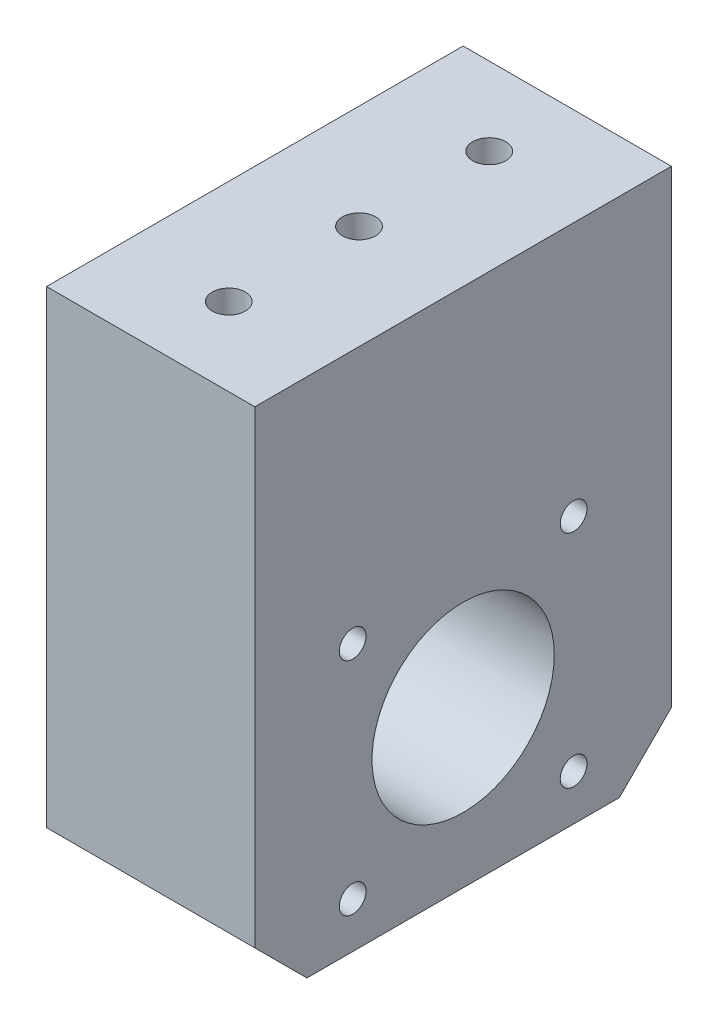
SolidWorks part; units mm, degrees
material "Nylon 6/10"
ref_plane "Front Plane" through (0, 0, 0) normal (0, 0, 1) x (1, 0, 0)
ref_plane "Top Plane" through (0, 0, 0) normal (0, 1, 0) x (1, 0, 0)
ref_plane "Right Plane" through (0, 0, 0) normal (1, 0, 0) x (0, 0, -1)
sketch "Sketch1" plane through (0, 0, 0) normal (1, 0, 0) x (0, 0, -1)
  line L1 (-25.4, -31.75) -> (25.4, -31.75)
  line L2 (-25.4, -31.75) -> (-25.4, 31.75)
  line L3 (-25.4, 31.75) -> (25.4, 31.75)
  line L4 (25.4, -31.75) -> (25.4, 31.75)
  line L5 (-25.4, -31.75) -> (25.4, 31.75) construction
  line L6 (-25.4, 31.75) -> (25.4, -31.75) construction
  point P0 (0, 0)
  dimension "D1" = 50.8
  dimension "D2" = 63.5
extrude "Base" add sketch "Sketch1" along normal blind 25.4
hole_wizard "7/8 (0.875) Diameter Hole1" positions "Sketch3" profile "Sketch2" hole size "7/8" standard "ANSI Inch" end condition through all
sketch "Sketch3" plane through (25.4, 0, 0) normal (1, 0, 0) x (0, 0, -1)
  line L1 (25.4, 31.75) -> (-25.4, 31.75) construction
  line L2 (0, -31.75) -> (0, 31.75) construction
  line L3 (-25.4, -31.75) -> (25.4, -31.75) construction
  point P0 (0, -12.7)
  dimension "D1" = 44.45
sketch "Sketch2" plane through (25.4, -12.7, 0) normal (0, 1, 0) x (0, 0, -1)
  line L0 (0, 0) -> (0, 25.4)
  line L1 (0, 25.4) -> (11.1125, 25.4)
  line L2 (11.1125, 25.4) -> (11.1125, 0)
  line L5 (11.1125, 0) -> (0, 0)
  line L11 (0, -6.35) -> (0, 107.95) construction
  dimension "Thru Hole Dia." = 22.225
  dimension "Thru Hole Depth" = 25.4
hole_wizard "#10-32 Tapped Hole1" positions "Sketch12" profile "Sketch11" tap size "#10-32" standard "ANSI Inch"
sketch "Sketch12" plane through (0, 31.75, 0) normal (0, 1, 0) x (1, 0, 0)
  line L0 (12.7, 25.4) -> (12.7, -25.4) construction
  line L1 (25.4, 25.4) -> (0, 25.4) construction
  line L2 (25.4, -25.4) -> (0, -25.4) construction
  line L3 (25.4, 0) -> (0, 0) construction
  line L4 (25.4, 25.4) -> (25.4, -25.4) construction
  line L5 (0, 25.4) -> (0, -25.4) construction
  point P0 (12.7, 15.875)
  point P2 (12.7, -15.875)
  point P13 (12.7, 0)
  dimension "D1" = 9.525
  dimension "D2" = 9.525
sketch "Sketch11" plane through (12.7, 31.75, -15.875) normal (1, 0, 0) x (0, 0, 1)
  line L0 (0, 0) -> (0, 26.6133)
  line L1 (0, 26.6133) -> (2.0193, 25.4)
  line L2 (2.0193, 25.4) -> (2.0193, 0)
  line L5 (2.0193, 0) -> (0, 0)
  line L10 (0, 26.6133) -> (-2.0193, 25.4) construction
  line L11 (0, -6.35) -> (0, 107.95) construction
  dimension "Tap Drill Dia." = 4.0386
  dimension "Tap Drill Depth" = 25.4
  dimension "Drill Angle" = 118
hole_wizard "CBORE for #4 Socket Head Cap Screw1" positions "Sketch14" profile "Sketch13" counterbore size "#4" standard "ANSI Inch" end condition through all
sketch "Sketch14" plane through (0, 0, 0) normal (-1, 0, 0) x (0, 0, 1)
  line L0 (0, 31.75) -> (0, -31.75) construction
  line L1 (-25.4, 31.75) -> (25.4, 31.75) construction
  line L2 (25.4, -31.75) -> (-25.4, -31.75) construction
  line L3 (0, -12.7) -> (-13.4704, 0.7704) construction
  circle A1 centre (0, -12.7) radius 11.1125 construction
  circle A2 centre (0, -12.7) radius 11.1125
  point P0 (-13.4704, 0.7704)
  dimension "D1" = 19.05
  dimension "D2" = 45
sketch "Sketch13" plane through (0, 0.7704, -13.4704) normal (0, 1, 0) x (0, 0, 1)
  line L0 (0, 0) -> (0, 25.4)
  line L1 (0, 25.4) -> (1.6319, 25.4)
  line L3 (1.6319, 25.4) -> (1.632, 2.8448)
  line L4 (1.632, 2.8448) -> (2.7788, 2.8448)
  line L5 (2.7788, 2.8448) -> (2.7788, 0)
  line L7 (2.7788, 0) -> (0, 0)
  line L11 (0, -6.35) -> (0, 107.95) construction
  dimension "Thru Hole Dia." = 3.2639
  dimension "Thru Hole Depth" = 25.4
  dimension "C'Bore Dia." = 5.5575
  dimension "C'Bore Depth" = 2.8448
pattern_circular "CirPattern1" count 4 over 360 about axis through (0, -12.7, 0) along (1, 0, 0) of "CBORE for #4 Socket Head Cap Screw1"
chamfer "Chamfer2" distance 6.35 angle 45 2 edges at (12.7, -31.75, 25.4) (12.7, -31.75, -25.4)
